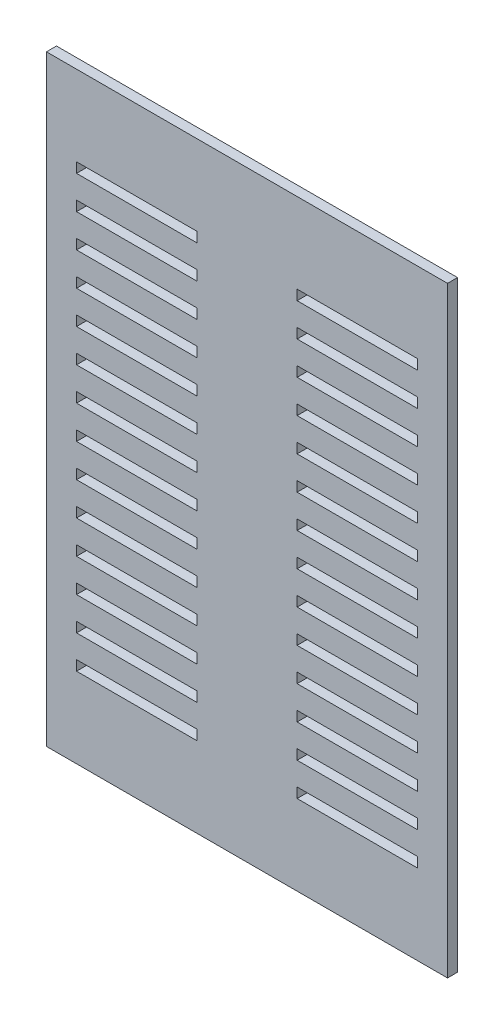
SolidWorks part; units mm, degrees
ref_plane "Alzado" through (0, 0, 0) normal (0, 0, 1) x (1, 0, 0)
ref_plane "Planta" through (0, 0, 0) normal (0, 1, 0) x (1, 0, 0)
ref_plane "Vista lateral" through (0, 0, 0) normal (1, 0, 0) x (0, 0, -1)
sketch "Croquis1" plane through (0, 0, 0) normal (0, 0, 1) x (1, 0, 0)
  line L1 (-100, -150) -> (100, -150)
  line L2 (-100, -150) -> (-100, 150)
  line L3 (-100, 150) -> (100, 150)
  line L4 (100, -150) -> (100, 150)
  line L5 (-100, -150) -> (100, 150) construction
  line L6 (-100, 150) -> (100, -150) construction
  point P0 (0, 0)
  dimension "D1" = 200
  dimension "D2" = 300
extrude "Saliente-Extruir1" add sketch "Croquis1" along normal blind 5
sketch "Croquis2" plane through (0, 0, 5) normal (0, 0, 1) x (1, 0, 0)
  line L0 (100, 150) -> (-100, 150) construction
  line L1 (-85, 110) -> (-25, 110)
  line L2 (-85, 110) -> (-85, 105)
  line L3 (-85, 105) -> (-25, 105)
  line L4 (-25, 110) -> (-25, 105)
  line L5 (-100, 150) -> (-100, -150) construction
  line L6 (25, 110) -> (85, 110)
  line L7 (25, 105) -> (85, 105)
  line L8 (85, 110) -> (85, 105)
  line L9 (25, 110) -> (25, 105)
  line L10 (25, 93.4615) -> (85, 93.4615)
  line L11 (25, 88.4615) -> (85, 88.4615)
  line L12 (85, 93.4615) -> (85, 88.4615)
  line L13 (25, 93.4615) -> (25, 88.4615)
  line L14 (25, 76.9231) -> (85, 76.9231)
  line L15 (25, 71.9231) -> (85, 71.9231)
  line L16 (85, 76.9231) -> (85, 71.9231)
  line L17 (25, 76.9231) -> (25, 71.9231)
  line L18 (25, 60.3846) -> (85, 60.3846)
  line L19 (25, 55.3846) -> (85, 55.3846)
  line L20 (85, 60.3846) -> (85, 55.3846)
  line L21 (25, 60.3846) -> (25, 55.3846)
  line L22 (25, 43.8462) -> (85, 43.8462)
  line L23 (25, 38.8462) -> (85, 38.8462)
  line L24 (85, 43.8462) -> (85, 38.8462)
  line L25 (25, 43.8462) -> (25, 38.8462)
  line L26 (25, 27.3077) -> (85, 27.3077)
  line L27 (25, 22.3077) -> (85, 22.3077)
  line L28 (85, 27.3077) -> (85, 22.3077)
  line L29 (25, 27.3077) -> (25, 22.3077)
  line L30 (25, 10.7692) -> (85, 10.7692)
  line L31 (25, 5.7692) -> (85, 5.7692)
  line L32 (85, 10.7692) -> (85, 5.7692)
  line L33 (25, 10.7692) -> (25, 5.7692)
  line L34 (25, -5.7692) -> (85, -5.7692)
  line L35 (25, -10.7692) -> (85, -10.7692)
  line L36 (85, -5.7692) -> (85, -10.7692)
  line L37 (25, -5.7692) -> (25, -10.7692)
  line L38 (25, -22.3077) -> (85, -22.3077)
  line L39 (25, -27.3077) -> (85, -27.3077)
  line L40 (85, -22.3077) -> (85, -27.3077)
  line L41 (25, -22.3077) -> (25, -27.3077)
  line L42 (25, -38.8462) -> (85, -38.8462)
  line L43 (25, -43.8462) -> (85, -43.8462)
  line L44 (85, -38.8462) -> (85, -43.8462)
  line L45 (25, -38.8462) -> (25, -43.8462)
  line L46 (25, -55.3846) -> (85, -55.3846)
  line L47 (25, -60.3846) -> (85, -60.3846)
  line L48 (85, -55.3846) -> (85, -60.3846)
  line L49 (25, -55.3846) -> (25, -60.3846)
  line L50 (25, -71.9231) -> (85, -71.9231)
  line L51 (25, -76.9231) -> (85, -76.9231)
  line L52 (85, -71.9231) -> (85, -76.9231)
  line L53 (25, -71.9231) -> (25, -76.9231)
  line L54 (25, -88.4615) -> (85, -88.4615)
  line L55 (25, -93.4615) -> (85, -93.4615)
  line L56 (85, -88.4615) -> (85, -93.4615)
  line L57 (25, -88.4615) -> (25, -93.4615)
  line L58 (25, -105) -> (85, -105)
  line L59 (25, -110) -> (85, -110)
  line L60 (85, -105) -> (85, -110)
  line L61 (25, -105) -> (25, -110)
  line L62 (-85, 93.4615) -> (-25, 93.4615)
  line L63 (-85, 88.4615) -> (-25, 88.4615)
  line L64 (-25, 93.4615) -> (-25, 88.4615)
  line L65 (-85, 93.4615) -> (-85, 88.4615)
  line L66 (-85, 76.9231) -> (-25, 76.9231)
  line L67 (-85, 71.9231) -> (-25, 71.9231)
  line L68 (-25, 76.9231) -> (-25, 71.9231)
  line L69 (-85, 76.9231) -> (-85, 71.9231)
  line L70 (-85, 60.3846) -> (-25, 60.3846)
  line L71 (-85, 55.3846) -> (-25, 55.3846)
  line L72 (-25, 60.3846) -> (-25, 55.3846)
  line L73 (-85, 60.3846) -> (-85, 55.3846)
  line L74 (-85, 43.8462) -> (-25, 43.8462)
  line L75 (-85, 38.8462) -> (-25, 38.8462)
  line L76 (-25, 43.8462) -> (-25, 38.8462)
  line L77 (-85, 43.8462) -> (-85, 38.8462)
  line L78 (-85, 27.3077) -> (-25, 27.3077)
  line L79 (-85, 22.3077) -> (-25, 22.3077)
  line L80 (-25, 27.3077) -> (-25, 22.3077)
  line L81 (-85, 27.3077) -> (-85, 22.3077)
  line L82 (-85, 10.7692) -> (-25, 10.7692)
  line L83 (-85, 5.7692) -> (-25, 5.7692)
  line L84 (-25, 10.7692) -> (-25, 5.7692)
  line L85 (-85, 10.7692) -> (-85, 5.7692)
  line L86 (-85, -5.7692) -> (-25, -5.7692)
  line L87 (-85, -10.7692) -> (-25, -10.7692)
  line L88 (-25, -5.7692) -> (-25, -10.7692)
  line L89 (-85, -5.7692) -> (-85, -10.7692)
  line L90 (-85, -22.3077) -> (-25, -22.3077)
  line L91 (-85, -27.3077) -> (-25, -27.3077)
  line L92 (-25, -22.3077) -> (-25, -27.3077)
  line L93 (-85, -22.3077) -> (-85, -27.3077)
  line L94 (-85, -38.8462) -> (-25, -38.8462)
  line L95 (-85, -43.8462) -> (-25, -43.8462)
  line L96 (-25, -38.8462) -> (-25, -43.8462)
  line L97 (-85, -38.8462) -> (-85, -43.8462)
  line L98 (-85, -55.3846) -> (-25, -55.3846)
  line L99 (-85, -60.3846) -> (-25, -60.3846)
  line L100 (-25, -55.3846) -> (-25, -60.3846)
  line L101 (-85, -55.3846) -> (-85, -60.3846)
  line L102 (-85, -71.9231) -> (-25, -71.9231)
  line L103 (-85, -76.9231) -> (-25, -76.9231)
  line L104 (-25, -71.9231) -> (-25, -76.9231)
  line L105 (-85, -71.9231) -> (-85, -76.9231)
  line L106 (-85, -88.4615) -> (-25, -88.4615)
  line L107 (-85, -93.4615) -> (-25, -93.4615)
  line L108 (-25, -88.4615) -> (-25, -93.4615)
  line L109 (-85, -88.4615) -> (-85, -93.4615)
  line L110 (-85, -105) -> (-25, -105)
  line L111 (-85, -110) -> (-25, -110)
  line L112 (-25, -105) -> (-25, -110)
  line L113 (-85, -105) -> (-85, -110)
  line L114 (-100, -150) -> (100, -150) construction
  line L115 (100, -150) -> (100, 150) construction
  dimension "D1" = 60
  dimension "D2" = 5
  dimension "D3" = 40
  dimension "D4" = 15
  dimension "D5" = 2
  dimension "D7" = 40
  dimension "D8" = 15
  dimension "D6" = 14
extrude "Cortar-Extruir1" cut sketch "Croquis2" against normal through all
